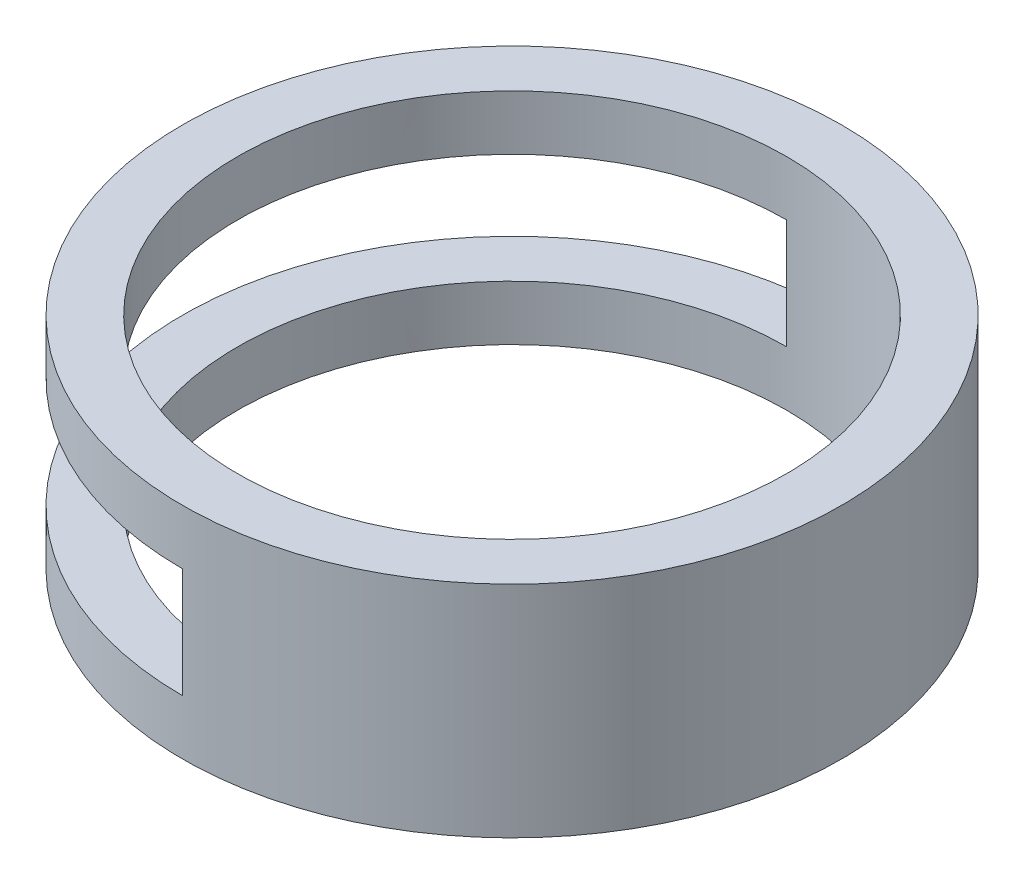
SolidWorks part; units mm, degrees
ref_plane "Front Plane" through (0, 0, 0) normal (0, 0, 1) x (1, 0, 0)
ref_plane "Top Plane" through (0, 0, 0) normal (0, 1, 0) x (1, 0, 0)
ref_plane "Right Plane" through (0, 0, 0) normal (1, 0, 0) x (0, 0, -1)
sketch "Sketch1" plane through (0, 0, 0) normal (0, 0, 1) x (1, 0, 0)
  line L2 (-5, 0) -> (-5, -20)
  line L10 (0, 0) -> (0, -20)
  line L11 (-5, 0) -> (0, 0)
  line L12 (-5, -20) -> (0, -20)
  line L13 (-5, -5) -> (0, -5)
  line L14 (0, -5) -> (0, -15)
  line L15 (0, -15) -> (-5, -15)
  line L16 (-5, -15) -> (-5, -5)
  line L17 (25, -980.0656) -> (25, 49019.9344) construction
  line L18 (0, 0) -> (0, -20)
  dimension "D1" = 0
  dimension "D2" = 20
  dimension "D3" = 5
  dimension "D4" = 5
  dimension "D5" = 5
  dimension "D6" = 25
revolve "Revolve5" add sketch "Sketch1" angle 360 about L17
revolve "Cut-Revolve5" cut sketch "Sketch1<12>" angle 180 mid plane about L17
sketch "Sketch1<12>" plane through (0, 0, 0) normal (0, 0, 1) x (1, 0, 0) same geometry as "Sketch1"
